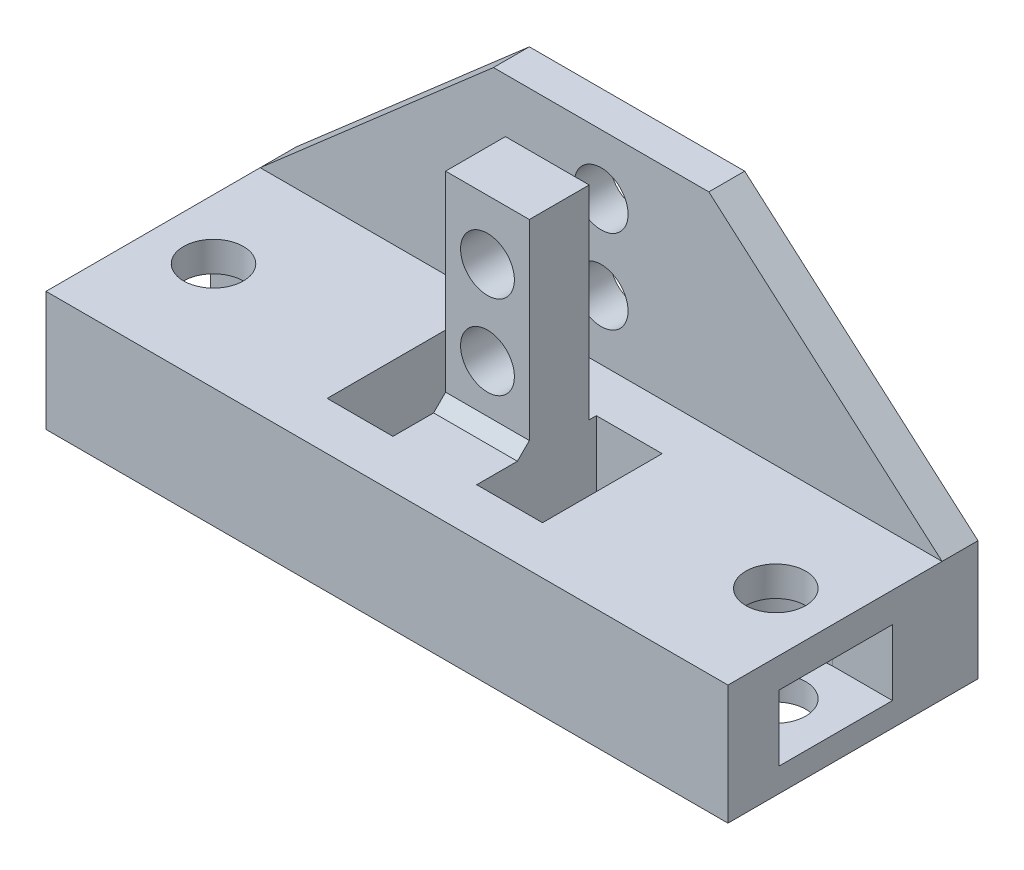
SolidWorks part; units mm, degrees
ref_plane "Plan de face" through (0, 0, 0) normal (0, 0, 1) x (1, 0, 0)
ref_plane "Plan de dessus" through (0, 0, 0) normal (0, 1, 0) x (1, 0, 0)
ref_plane "Plan de droite" through (0, 0, 0) normal (1, 0, 0) x (0, 0, -1)
sketch "Esquisse1" plane through (0, 0, 0) normal (0, 0, 1) x (1, 0, 0)
  line L0 (0, 17) -> (20, 17)
  line L1 (0, 0) -> (20, 0)
  line L2 (0, 0) -> (0, 25.6902)
  line L3 (0, 25.6902) -> (20, 25.6902)
  line L4 (20, 0) -> (20, 25.6902)
  circle A0 centre (10, 5) radius 2.1
  circle A1 centre (10, 12) radius 2.1
  dimension "D2" = 4.2
  dimension "D3" = 4.2
  dimension "D1" = 20
  dimension "D5" = 10
  dimension "D6" = 5
  dimension "D7" = 7
  dimension "D9" = 17
  dimension "D11" = 10
extrude "Boss.-Extru.1" add sketch "Esquisse1" along normal blind 5 contours L1 L4 L0 L2 A1 A0 region at (10, 8.5, 0)
sketch "Esquisse2" plane through (0, 0, 0) normal (0, -1, 0) x (1, 0, 0)
  line L0 (20, 5) -> (20, 0) construction
  line L1 (0, 0) -> (20, 0)
  line L2 (0, 0) -> (0, 5)
  line L3 (0, 5) -> (20, 5)
  line L4 (20, 0) -> (20, 5)
  line L5 (1, 5) -> (1, 0)
  line L6 (19, 5) -> (19, 0)
  line L7 (1, 3) -> (19, 3)
  line L9 (1, 0) -> (19, 0)
  line L10 (1, 0) -> (1, -5)
  line L11 (1, -5) -> (19, -5)
  line L12 (19, 0) -> (19, -5)
  line L13 (1, 0) -> (19, 0)
  line L14 (1, 0) -> (1, -0.6)
  line L15 (1, -0.6) -> (19, -0.6)
  line L16 (19, 0) -> (19, -0.6)
  point P11 (19, 2.5)
  dimension "D1" = 5
  dimension "D2" = 18
  dimension "D3" = 1
  dimension "D4" = 3
  dimension "D5" = 5
  dimension "D6" = 0.6
extrude "Boss.-Extru.3" add sketch "Esquisse2" along normal blind 10 contours L15 L10 L11 L12 region at (10, 0, -2.8)
sketch "Esquisse5" plane through (0, 0, 5) normal (0, 0, 1) x (1, 0, 0)
  line L0 (13.5, 17) -> (13.5, 0)
  line L1 (0, 17) -> (20, 17) construction
  line L2 (0, 0) -> (20, 0) construction
  line L3 (13.5, 0) -> (20, 0)
  line L4 (20, 0) -> (20, 17)
  line L5 (20, 0) -> (20, 17) construction
  line L6 (20, 17) -> (13.5, 17)
  line L8 (0, 0) -> (6.5, 0)
  line L9 (0, 0) -> (0, 17)
  line L10 (0, 17) -> (6.5, 17)
  line L11 (6.5, 0) -> (6.5, 17)
  dimension "D1" = 6.5
  dimension "D2" = 6.5
extrude "Enlèv. mat.-Extru.3" cut sketch "Esquisse5" against normal blind 18
sketch "Esquisse10" plane through (0, 0, 5) normal (0, 0, 1) x (1, 0, 0)
  line L1 (6.5, 0) -> (13.5, 0)
  line L2 (6.5, 0) -> (6.5, -10)
  line L3 (6.5, -10) -> (13.5, -10)
  line L4 (13.5, 0) -> (13.5, -10)
  dimension "D1" = 7
  dimension "D2" = 10
extrude "Boss.-Extru.6" add sketch "Esquisse10" against normal blind 10 and the other way blind 8.4
sketch "Esquisse11" plane through (0, 0, 0) normal (0, 1, 0) x (1, 0, 0)
  line L0 (6.5, 0.6) -> (6.5, 0) construction
  line L1 (6.5, 0) -> (13.5, 0)
  line L2 (6.5, 0) -> (6.5, 5)
  line L3 (6.5, 5) -> (13.5, 5)
  line L4 (13.5, 0) -> (13.5, 5)
  line L5 (6.5, 0) -> (13.5, 0) construction
  line L6 (1, 5) -> (19, 5) construction
  line L8 (13.5, 4.5) -> (6.5, 4.5)
  line L9 (13.5, 4.5) -> (13.5, 0)
  line L10 (13.5, 0) -> (6.5, 0)
  line L11 (6.5, 4.5) -> (6.5, 0)
  line L12 (6.5, 4.5) -> (13.5, 4.5)
  line L13 (6.5, 4.5) -> (6.5, 7.5)
  line L14 (6.5, 7.5) -> (13.5, 7.5)
  line L15 (13.5, 4.5) -> (13.5, 7.5)
  line L16 (6.5, 4.5) -> (1, 4.5)
  line L17 (6.5, 4.5) -> (6.5, 7.5)
  line L18 (6.5, 7.5) -> (1, 7.5)
  line L19 (1, 4.5) -> (1, 7.5)
  line L20 (13.5, 4.5) -> (19, 4.5)
  line L21 (13.5, 4.5) -> (13.5, 7.5)
  line L22 (13.5, 7.5) -> (19, 7.5)
  line L23 (19, 4.5) -> (19, 7.5)
  line M12 (19, 0.6) -> (19, 5)
  line M13 (19, 5) -> (1, 5)
  line M14 (1, 5) -> (1, 0.6)
  dimension "D1" = 7
  dimension "D2" = 4.5
  dimension "D3" = 3
  dimension "D4" = 5.5
  dimension "D5" = 5.5
extrude "Boss.-Extru.7" add sketch "Esquisse11" along normal blind 17 contours L19 L13 L18 M13 | L15 L14 L13 M13 | L23 L22 L15 M13 | L16 L2 M13 M14 | L8 L4 L2 M13 | L4 L20 M12 M13 region at (3.75, 0, -4.75) region at (10, 0, -4.75) region at (16.25, 0, -4.75) region at (10, 0, -6.25) region at (3.75, 0, -6.25) region at (16.25, 0, -6.25)
sketch "Esquisse12" plane through (0, 0, 0) normal (0, -1, 0) x (1, 0, 0)
  line L5 (1, -5) -> (19, -5)
  line L6 (1, -5) -> (1, -7.5)
  line L7 (1, -7.5) -> (19, -7.5)
  line L8 (19, -5) -> (19, -7.5)
extrude "Boss.-Extru.8" add sketch "Esquisse12" along normal blind 10
sketch "Esquisse20" plane through (0, 0, 5) normal (0, 0, 1) x (1, 0, 0)
  circle A0 centre (10, 5) radius 2.25
  circle A1 centre (10, 12) radius 2.25
  dimension "D1" = 4.5
extrude "Enlèv. mat.-Extru.7" cut sketch "Esquisse20" against normal blind 18
sketch "Esquisse21" plane through (13.5, 0, 0) normal (1, 0, 0) x (0, 0, -1)
  line L0 (-13.4, -10) -> (0.6, -10) construction
  line L1 (-13.4, 0) -> (-9.4, 0)
  line L2 (-13.4, 0) -> (-13.4, -10)
  line L3 (-13.4, -10) -> (-9.4, -10)
  line L4 (-9.4, 0) -> (-9.4, -10)
  line L7 (0.6, 0) -> (7.5, 0)
  line L8 (0.6, 0) -> (0.6, -10)
  line L9 (0.6, -10) -> (7.5, -10)
  line L11 (7.5, 0) -> (7.5, -10)
  dimension "D1" = 4
  dimension "D2" = 6.9
extrude "Boss.-Extru.9" add sketch "Esquisse21" along normal blind 25
sketch "Esquisse22" plane through (0, 0, -0.6) normal (0, 0, 1) x (1, 0, 0)
  line L1 (38.5, -10) -> (13.5, -10) construction
  line L2 (38.5, 0) -> (19, 0)
  line L3 (38.5, 0) -> (38.5, -10)
  line L4 (38.5, -10) -> (19, -10)
  line L5 (19, 0) -> (19, -10)
  line L6 (13.5, 0) -> (13.5, -10) construction
  dimension "D1" = 5.5
extrude "Boss.-Extru.10" add sketch "Esquisse22" along normal up to surface (14 mm away) up to face at (22.5, -5, 13.4)
sketch "Esquisse24" plane through (0, 0, -7.5) normal (0, 0, -1) x (-1, 0, 0)
  line L0 (-38.5, 0) -> (-19, 0)
  line L2 (-19, 0) -> (-19, 17)
  line L5 (-19, 17) -> (-38.5, 0)
extrude "Boss.-Extru.11" add sketch "Esquisse24" against normal up to surface (3 mm away) up to face at (12.25, 12, -4.5)
ref_plane "Plan1" through (10, 0, 0) normal (-1, 0, 0) x (0, 0, 1)
mirror "Symétrie1" about plane through (10, 0, 0) normal (-1, 0, 0) of "Boss.-Extru.10", "Boss.-Extru.9", "Boss.-Extru.11"
chamfer "Chanfrein1" distance 1 angle 45 1 edges at (10, 0, 5)
sketch "Esquisse29" plane through (0, 0, 0) normal (0, 1, 0) x (1, 0, 0)
  line L0 (19, -9.4) -> (13.5, -9.4) construction
  line L1 (1, -9.4) -> (6.5, -9.4) construction
  line L2 (-18.5, 4.5) -> (-18.5, -13.4) construction
  line L3 (38.5, 4.5) -> (38.5, -13.4) construction
  circle A0 centre (-13.5, -4.4) radius 2.5
  circle A1 centre (33.5, -4.4) radius 2.5
  dimension "D3" = 5
  dimension "D4" = 5
  dimension "D5" = 5
  dimension "D1" = 5
  dimension "D2" = 5
  dimension "D6" = 5
extrude "Enlèv. mat.-Extru.11" cut sketch "Esquisse29" against normal blind 10
sketch "Esquisse30" plane through (0, -10, 0) normal (0, -1, 0) x (-1, 0, 0)
  line L1 (13.5, -9.15) -> (18.5, -9.15)
  line L2 (18.5, -13.4) -> (18.5, 7.5) construction
  line L3 (18.5, -9.15) -> (18.5, 0.35)
  line L4 (18.5, 0.35) -> (13.5, 0.35)
  circle A0 centre (13.5, -4.4) radius 4.75
  circle M8 centre (13.5, -4.4) radius 2.5
  line M15 (18.5, -13.4) -> (18.5, 7.5)
  dimension "D1" = 9.5
extrude "Enlèv. mat.-Extru.12" cut sketch "Esquisse30" against normal blind 5.5 from offset 2 contours A0 M8 | A0 L1 L4 M15 region at (-16.9347, -10, 7.8347) region at (-8.8844, -10, 4.4) offset against normal yes
mirror "Symétrie3" about plane through (10, 0, 0) normal (-1, 0, 0) of "Enlèv. mat.-Extru.12"
